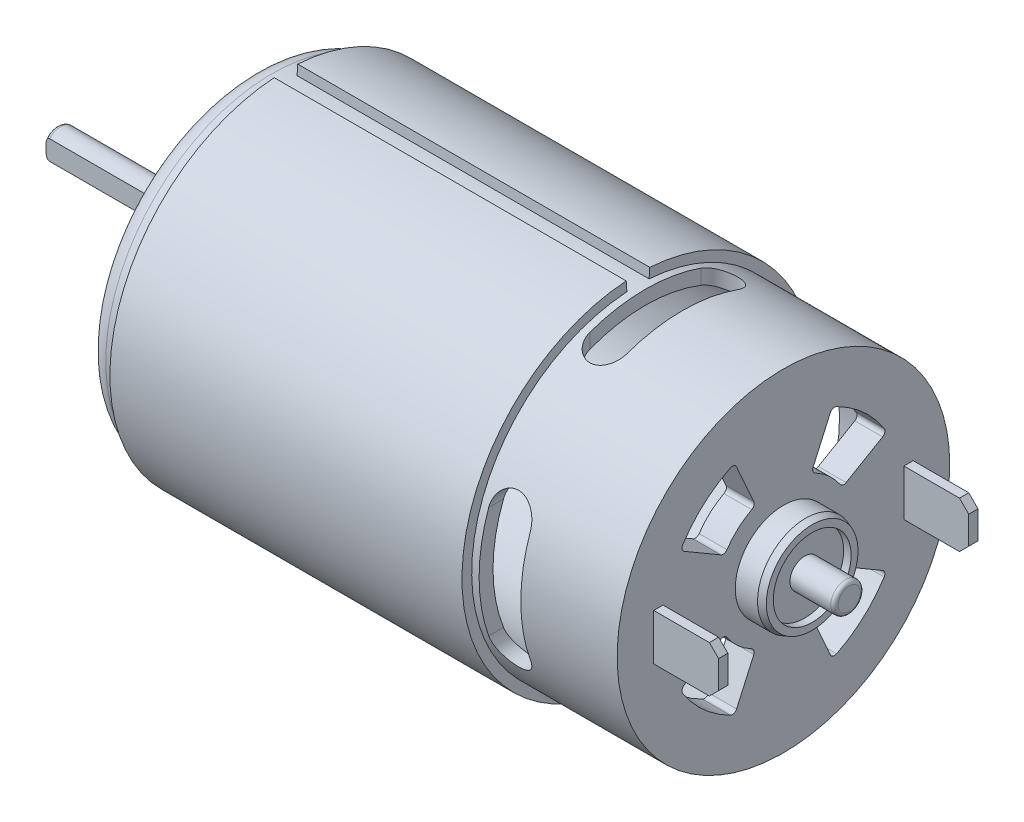
SolidWorks part; units mm, degrees
ref_plane "Спереди" through (0, 0, 0) normal (0, 0, 1) x (1, 0, 0)
ref_plane "Сверху" through (0, 0, 0) normal (0, 1, 0) x (1, 0, 0)
ref_plane "Справа" through (0, 0, 0) normal (1, 0, 0) x (0, 0, -1)
sketch "Эскиз1" plane through (0, 0, 0) normal (1, 0, 0) x (0, 0, -1)
  circle A0 centre (0, 0) radius 19
  dimension "D1" = 38
extrude "Бобышка-Вытянуть1" add sketch "Эскиз1" along normal blind 57.2
sketch "Эскиз2" plane through (57.2, 0, 0) normal (1, 0, 0) x (0, 0, -1)
  circle A0 centre (0, 0) radius 19
  circle A1 centre (0, 0) radius 17.95
  dimension "D1" = 38
  dimension "D2" = 35.9
extrude "Вырез-Вытянуть1" cut sketch "Эскиз2" against normal blind 15.7
sketch "Эскиз3" plane through (0, 0, 0) normal (-1, 0, 0) x (0, 0, 1)
  circle A0 centre (0, 0) radius 19
  circle A1 centre (0, 0) radius 17.95
  dimension "D1" = 38
  dimension "D2" = 35.9
extrude "Вырез-Вытянуть2" cut sketch "Эскиз3" against normal blind 3.5
fillet "Скругление1" radius 2 1 edges at (0, 0, 17.95)
sketch "Эскиз4" plane through (0, 0, 0) normal (0, 0, 1) x (1, 0, 0)
  line L0 (57.2, 0) -> (47.1754, 0) construction
  line L2 (44.55, -6) -> (44.55, 6) construction
  line L3 (42.3, -6) -> (42.3, 6)
  line L4 (46.8, -6) -> (46.8, 6)
  line L5 (41.5, -19) -> (41.5, 19) construction
  arc A0 (42.3, -6) -> (46.8, -6) centre (44.55, -6) ccw
  arc A1 (46.8, 6) -> (42.3, 6) centre (44.55, 6) ccw
  point P3 (44.55, 0)
  dimension "D1" = 12
  dimension "D2" = 2.25
  dimension "D3" = 0.8
extrude "Вырез-Вытянуть3" cut sketch "Эскиз4" against normal through all both and the other way through all
sketch "Эскиз5" plane through (0, 0, 0) normal (0, 1, 0) x (1, 0, 0)
  line L0 (44.3, 6) -> (44.3, -6) construction
  line L2 (46.0081, 0) -> (47.9808, 0) construction
  line L3 (46.3, 6) -> (46.3, -6)
  line L4 (42.3, 6) -> (42.3, -6)
  line L5 (41.5, -17.95) -> (41.5, 17.95) construction
  arc A0 (46.3, 6) -> (42.3, 6) centre (44.3, 6) ccw
  arc A1 (42.3, -6) -> (46.3, -6) centre (44.3, -6) ccw
  point P5 (44.3, 0)
  dimension "D1" = 0.8
  dimension "D2" = 2
  dimension "D3" = 12
extrude "Вырез-Вытянуть4" cut sketch "Эскиз5" against normal through all both and the other way through all
sketch "Эскиз6" plane through (0, 0, 0) normal (-1, 0, 0) x (0, 0, 1)
  circle A0 centre (0, 0) radius 6.55
  dimension "D1" = 13.1
extrude "Бобышка-Вытянуть2" add sketch "Эскиз6" along normal blind 4.5
sketch "Эскиз7" plane through (-4.5, 0, 0) normal (-1, 0, 0) x (0, 0, 1)
  circle A0 centre (0, 0) radius 5.65
  dimension "D1" = 11.3
extrude "Вырез-Вытянуть5" cut sketch "Эскиз7" against normal blind 0.8
sketch "Эскиз8" plane through (-3.7, 0, 0) normal (-1, 0, 0) x (0, 0, 1)
  circle A0 centre (0, 0) radius 1.6
  dimension "D1" = 3.2
extrude "Бобышка-Вытянуть3" add sketch "Эскиз8" along normal blind 17.5 separate body
fillet "Скругление2" radius 0.4 1 edges at (-21.2, 0, 1.6)
sketch "Эскиз9" plane through (-21.2, 0, 0) normal (-1, 0, 0) x (0, 0, 1)
  line L0 (1.6, 0) -> (1.2, 0) construction
  line L1 (1.2, 1.0583) -> (1.2, -1.0583)
  arc A0 (1.2, -1.0583) -> (1.2, 1.0583) centre (0, 0) ccw
  dimension "D1" = 3.2
  dimension "D2" = 0.4
extrude "Вырез-Вытянуть6" cut sketch "Эскиз9" against normal blind 12.8
chamfer "Фаска1" distance 0.7 angle 20 1 edges at (-4.5, 0, 6.55) first distance on face at (-4.5, 0, 6.55)
sketch "Эскиз10" plane through (0, 0, 0) normal (-1, 0, 0) x (0, 0, 1)
  line L0 (0, 0) -> (0, 9.0822) construction
  line L1 (0, 0) -> (-24.7697, 0) construction
  line L2 (-2.1822, 11.2467) -> (-1.7995, 9.2743)
  line L3 (-10.6113, 4.3186) -> (-8.7503, 3.5612)
  line L4 (-10.6113, -4.3186) -> (-8.7503, -3.5612)
  line L5 (-2.1822, -11.2467) -> (-1.7995, -9.2743)
  line L6 (2.1822, -11.2467) -> (1.7995, -9.2743)
  line L7 (10.6113, -4.3186) -> (8.7503, -3.5612)
  line L8 (2.1822, 11.2467) -> (1.7995, 9.2743)
  line L9 (10.6113, 4.3186) -> (8.7503, 3.5612)
  arc A0 (2, 10.3078) -> (9.7254, 3.9581) centre (0, 0) cw construction
  arc A1 (11.1243, 5.7009) -> (3.439, 12.0176) centre (0, 0) ccw
  arc A2 (7.4919, 4.0151) -> (2.4884, 8.1276) centre (0, 0) ccw
  arc A3 (-11.1243, 5.7009) -> (-10.6113, 4.3186) centre (-10.2343, 5.2449) ccw
  arc A4 (-7.4919, 4.0151) -> (-8.7503, 3.5612) centre (-8.3733, 4.4875) cw
  arc A5 (2, -10.3078) -> (9.7254, -3.9581) centre (0, 0) ccw construction
  arc A6 (11.1243, -5.7009) -> (3.439, -12.0176) centre (0, 0) cw
  arc A7 (7.4919, -4.0151) -> (2.4884, -8.1276) centre (0, 0) cw
  arc A8 (-1.7995, 9.2743) -> (-2.4884, 8.1276) centre (-2.7812, 9.0838) cw
  arc A9 (-2.1822, 11.2467) -> (-3.439, 12.0176) centre (-3.1639, 11.0562) ccw
  arc A10 (-2, 10.3078) -> (-9.7254, 3.9581) centre (0, 0) ccw construction
  arc A11 (-11.1243, 5.7009) -> (-3.439, 12.0176) centre (0, 0) cw
  arc A12 (-7.4919, 4.0151) -> (-2.4884, 8.1276) centre (0, 0) cw
  arc A13 (11.1243, 5.7009) -> (10.6113, 4.3186) centre (10.2343, 5.2449) cw
  arc A14 (3.439, 12.0176) -> (2.1822, 11.2467) centre (3.1639, 11.0562) ccw
  arc A15 (-2, -10.3078) -> (-9.7254, -3.9581) centre (0, 0) cw construction
  arc A16 (-11.1243, -5.7009) -> (-3.439, -12.0176) centre (0, 0) ccw
  arc A17 (-7.4919, -4.0151) -> (-2.4884, -8.1276) centre (0, 0) ccw
  arc A18 (2.4884, 8.1276) -> (1.7995, 9.2743) centre (2.7812, 9.0838) cw
  arc A19 (7.4919, 4.0151) -> (8.7503, 3.5612) centre (8.3733, 4.4875) ccw
  arc A20 (8.7503, -3.5612) -> (7.4919, -4.0151) centre (8.3733, -4.4875) ccw
  arc A21 (10.6113, -4.3186) -> (11.1243, -5.7009) centre (10.2343, -5.2449) cw
  arc A22 (2.1822, -11.2467) -> (3.439, -12.0176) centre (3.1639, -11.0562) ccw
  arc A23 (1.7995, -9.2743) -> (2.4884, -8.1276) centre (2.7812, -9.0838) cw
  arc A24 (-10.6113, -4.3186) -> (-11.1243, -5.7009) centre (-10.2343, -5.2449) ccw
  arc A25 (-1.7995, -9.2743) -> (-2.4884, -8.1276) centre (-2.7812, -9.0838) ccw
  arc A26 (-3.439, -12.0176) -> (-2.1822, -11.2467) centre (-3.1639, -11.0562) ccw
  arc A27 (-7.4919, -4.0151) -> (-8.7503, -3.5612) centre (-8.3733, -4.4875) ccw
  point P4 (6.6671, 8.1117)
  point P17 (6.6671, -8.1117)
  point P24 (-6.6671, 8.1117)
  point P31 (-6.6671, -8.1117)
  dimension "D1" = 10.5
  dimension "D2" = 4
  dimension "D5" = 8.5
  dimension "D6" = 12.5
  dimension "D7" = 8.5
  dimension "D8" = 1
  dimension "D3" = 10
  dimension "D4" = 2
extrude "Вырез-Вытянуть7" cut sketch "Эскиз10" against normal offset from surface (54.2 mm away) 3 up to face at (57.2, 0, -17.95)
sketch "Эскиз11" plane through (0, 0, 0) normal (-1, 0, 0) x (0, 0, 1)
  line L0 (0.3078, 0) -> (0.3078, 4.5379) construction
  circle A0 centre (-12.2672, 0) radius 1.4
  circle A1 centre (12.8828, 0) radius 1.4
  dimension "D1" = 2.8
  dimension "D2" = 25.15
extrude "Вырез-Вытянуть8" cut sketch "Эскиз11" against normal offset from surface (54.2 mm away) 3 up to face at (57.2, 0, -17.95)
sketch "Эскиз12" plane through (3.5, 0, 0) normal (-1, 0, 0) x (0, 0, 1)
  line L0 (0, 0) -> (0, 24.5291) construction
  line L1 (-1.2, 17.9098) -> (-1.2702, 18.9575)
  line L2 (1.2, 17.9098) -> (1.2702, 18.9575)
  line L3 (0, 0) -> (-1.7118, 25.5491) construction
  line L4 (0, 0) -> (1.6553, 24.7044) construction
  circle A0 centre (0, 0) radius 19 construction
  arc A2 (-1.2, 17.9098) -> (1.2, 17.9098) centre (0, 0) cw
  circle A3 centre (0, 0) radius 17.95 construction
  circle A4 centre (0, 0) radius 19 construction
  arc A5 (1.2702, 18.9575) -> (-1.2702, 18.9575) centre (0, 0) ccw
  dimension "D1" = 2.4
extrude "Вырез-Вытянуть9" cut sketch "Эскиз12" against normal through all both and the other way through all
sketch "Эскиз13" plane through (42.3, 0, 0) normal (1, 0, 0) x (0, 0, -1)
  circle A0 centre (0, 0) radius 16.45
  arc A1 (-1.2, 17.9098) -> (1.2, 17.9098) centre (0, 0) ccw construction
  dimension "D1" = 1.5
extrude "Вырез-Вытянуть10" cut sketch "Эскиз13" along normal offset from surface 3 and the other way offset from surface 1 up to face at (57.2, 0, -17.95) other way up to face at (0, 0, 14.2828)
sketch "Эскиз14" plane through (57.2, 0, 0) normal (1, 0, 0) x (0, 0, -1)
  line L0 (5.2653, -11.7765) -> (3, -6.7099)
  line L1 (11.1424, -6.5005) -> (6.3486, -3.7037)
  line L2 (-11.1424, -6.5005) -> (-6.3486, -3.7037)
  line L3 (-5.2653, -11.7765) -> (-3, -6.7099)
  line L4 (0, 0) -> (0, 12.2606) construction
  line L5 (6.3486, 3.7037) -> (11.1424, 6.5005)
  line L6 (3, 6.7099) -> (5.2653, 11.7765)
  line L7 (-3, 6.7099) -> (-5.2653, 11.7765)
  line L8 (-6.3486, 3.7037) -> (-11.1424, 6.5005)
  arc A0 (-6.3486, -3.7037) -> (-3, -6.7099) centre (0, 0) ccw
  arc A1 (-11.1424, -6.5005) -> (-5.2653, -11.7765) centre (0, 0) ccw
  arc A2 (6.3486, 3.7037) -> (3, 6.7099) centre (0, 0) ccw
  arc A3 (11.1424, 6.5005) -> (5.2653, 11.7765) centre (0, 0) ccw
  arc A4 (-5.2653, 11.7765) -> (-11.1424, 6.5005) centre (0, 0) ccw
  arc A5 (-3, 6.7099) -> (-6.3486, 3.7037) centre (0, 0) ccw
  arc A6 (3, -6.7099) -> (6.3486, -3.7037) centre (0, 0) ccw
  arc A7 (5.2653, -11.7765) -> (11.1424, -6.5005) centre (0, 0) ccw
  dimension "D1" = 14.7
  dimension "D2" = 25.8
  dimension "D3" = 6
  dimension "D4" = 4.5
extrude "Вырез-Вытянуть11" cut sketch "Эскиз14" against normal up to next (3 mm away)
fillet "Скругление3" radius 0.5 16 edges at (55.7, -11.7765, 5.2653) (55.7, -6.5005, 11.1424) (55.7, -3.7037, 6.3486) (55.7, -6.7099, 3) (55.7, -11.7765, -5.2653) (55.7, -6.7099, -3) (55.7, -3.7037, -6.3486) (55.7, -6.5005, -11.1424) (55.7, 3.7037, -6.3486) (55.7, 6.7099, -3) (55.7, 11.7765, -5.2653) (55.7, 6.5005, -11.1424) (55.7, 3.7037, 6.3486) (55.7, 6.5005, 11.1424) (55.7, 11.7765, 5.2653) (55.7, 6.7099, 3)
sketch "Эскиз15" plane through (57.2, 0, 0) normal (1, 0, 0) x (0, 0, -1)
  circle A0 centre (0, 0) radius 5.2
extrude "Бобышка-Вытянуть4" add sketch "Эскиз15" along normal blind 3.1
chamfer "Фаска2" distance 0.7 angle 20 1 edges at (60.3, 0, -5.2) first distance on face at (60.3, 0, -5.2)
sketch "Эскиз16" plane through (60.3, 0, 0) normal (1, 0, 0) x (0, 0, -1)
  circle A0 centre (0, 0) radius 4.2
  circle A1 centre (0, 0) radius 5.2 construction
  dimension "D1" = 1
extrude "Вырез-Вытянуть12" cut sketch "Эскиз16" against normal blind 0.8
sketch "Эскиз17" plane through (59.5, 0, 0) normal (1, 0, 0) x (0, 0, -1)
  circle A0 centre (0, 0) radius 1.6
extrude "Бобышка-Вытянуть5" add sketch "Эскиз17" along normal blind 4.8 separate body
fillet "Скругление4" radius 0.4 1 edges at (64.3, 0, -1.6)
sketch "Эскиз18" plane through (57.2, 0, 0) normal (1, 0, 0) x (0, 0, -1)
  line L0 (0, 0) -> (0, -11.144) construction
  line L1 (13, -2.6313) -> (14, -2.6313)
  line L2 (13, -2.6313) -> (13, 2.3687)
  line L3 (13, 2.3687) -> (14, 2.3687)
  line L4 (14, -2.6313) -> (14, 2.3687)
  line L5 (13, -2.6313) -> (14, 2.3687) construction
  line L6 (13, 2.3687) -> (14, -2.6313) construction
  line L7 (-14, -2.6313) -> (-13, -2.6313)
  line L8 (-14, -2.6313) -> (-14, 2.3687)
  line L9 (-14, 2.3687) -> (-13, 2.3687)
  line L10 (-13, -2.6313) -> (-13, 2.3687)
  line L11 (-14, -2.6313) -> (-13, 2.3687) construction
  line L12 (-14, 2.3687) -> (-13, -2.6313) construction
  point P0 (13.5, -0.1313)
  point P5 (-13.5, -0.1313)
  dimension "D1" = 13
  dimension "D2" = 13
extrude "Бобышка-Вытянуть6" add sketch "Эскиз18" along normal blind 7 separate body
chamfer "Фаска3" distance 1 angle 45 2 edges at (64.2, 2.3687, 13.5) (64.2, -2.6313, 13.5)
chamfer "Фаска4" distance 1 angle 45 2 edges at (64.2, -2.6313, -13.5) (64.2, 2.3687, -13.5)
